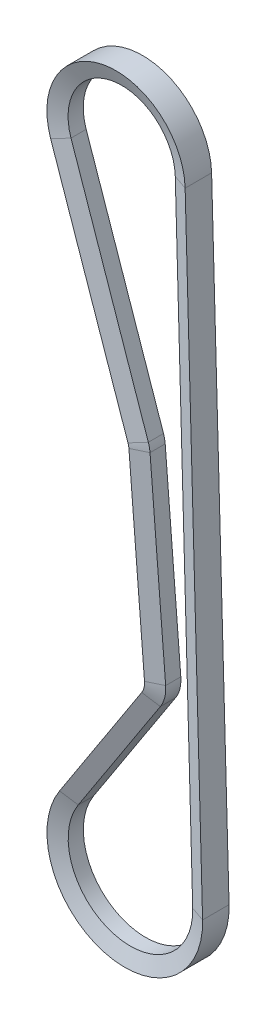
SolidWorks part; units mm, degrees
ref_plane "Front Plane" through (0, 0, 0) normal (0, 0, 1) x (1, 0, 0)
ref_plane "Top Plane" through (0, 0, 0) normal (0, 1, 0) x (1, 0, 0)
ref_plane "Right Plane" through (0, 0, 0) normal (1, 0, 0) x (0, 0, -1)
sketch "Sketch2" plane through (0, 0, 0) normal (0, 0, 1) x (1, 0, 0)
  line L0 (0, 0) -> (1, 0) construction
  line L1 (0, 0) -> (0, 1) construction
  line L12 (24.8653, 0.6939) -> (31.1415, -224.1968)
  line L14 (-20.3188, -209.7103) -> (9.2426, -164.2648)
  line L15 (10.2491, -160.2926) -> (4.6305, -90.5185)
  line L16 (4.3054, -88.962) -> (-23.5214, -8.0937)
  arc A4 (31.1415, -224.1968) -> (-20.3188, -209.7103) centre (3.1524, -224.9779) cw
  arc A7 (-23.5214, -8.0937) -> (24.8653, 0.6939) centre (0, 0) cw
  arc A8 (9.2426, -164.2648) -> (10.2491, -160.2926) centre (3.9196, -160.8023) ccw
  arc A9 (4.6305, -90.5185) -> (4.3054, -88.962) centre (-1.699, -91.0282) ccw
ref_plane "Plane4" through (-23.5214, -8.0937, 0) normal (-0.3254, 0.9456, 0) x (0.9456, 0.3254, 0)
sketch "Sketch3" plane through (-23.5214, -8.0937, 0) normal (-0.3254, 0.9456, 0) x (0.9456, 0.3254, 0)
  line L0 (0, -4.7625) -> (0, 4.7625)
  line L1 (0, -4.7625) -> (5.588, -2.7286)
  line L2 (5.588, -2.7286) -> (5.588, 2.7286)
  line L3 (5.588, 2.7286) -> (0, 4.7625)
  line L4 (0, 0) -> (5.588, 0) construction
  dimension "D1" = 9.525
  dimension "D2" = 5.588
  dimension "D3" = 40
sweep "Sweep1" add profiles "Sketch3" path "Sketch2"
